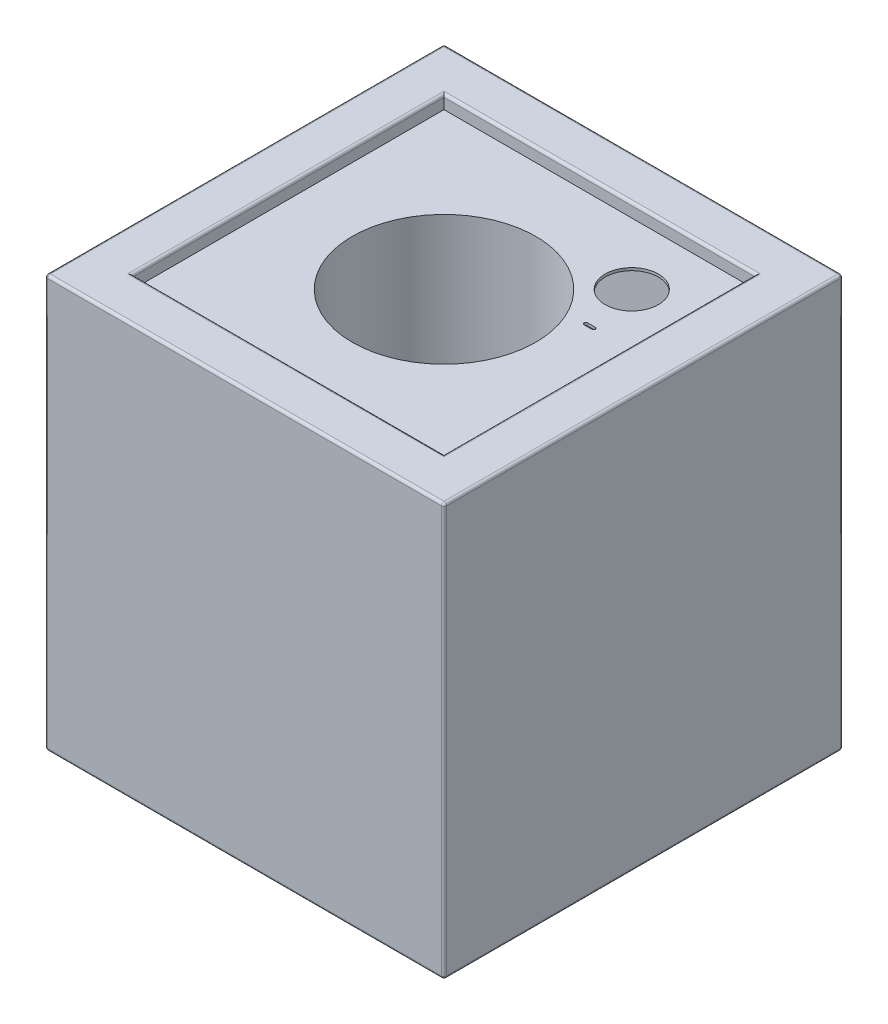
SolidWorks part; units mm, degrees
ref_plane "Front Plane" through (0, 0, 0) normal (0, 0, 1) x (1, 0, 0)
ref_plane "Top Plane" through (0, 0, 0) normal (0, 1, 0) x (1, 0, 0)
ref_plane "Right Plane" through (0, 0, 0) normal (1, 0, 0) x (0, 0, -1)
sketch "Sketch2" plane through (0, 0, 0) normal (0, 1, 0) x (1, 0, 0)
  line L1 (-150, 150) -> (150, 150)
  line L2 (-150, 150) -> (-150, -150)
  line L3 (-150, -150) -> (150, -150)
  line L4 (150, 150) -> (150, -150)
  line L5 (-150, 150) -> (150, -150) construction
  line L6 (-150, -150) -> (150, 150) construction
  point P0 (0, 0)
  dimension "D1" = 300
extrude "Boss-Extrude1" add sketch "Sketch2" along normal blind 10
sketch "Sketch3" plane through (0, 10, 0) normal (0, 1, 0) x (1, 0, 0)
  line L1 (-150, 150) -> (150, 150)
  line L2 (-150, 150) -> (-150, -150)
  line L3 (-150, -150) -> (150, -150)
  line L4 (150, 150) -> (150, -150)
  line L5 (-150, 150) -> (150, -150) construction
  line L6 (-150, -150) -> (150, 150) construction
  line L7 (-140, 140) -> (140, 140)
  line L8 (-140, 140) -> (-140, -140)
  line L9 (-140, -140) -> (140, -140)
  line L10 (140, 140) -> (140, -140)
  line L11 (-140, 140) -> (140, -140) construction
  line L12 (-140, -140) -> (140, 140) construction
  point P0 (0, 0)
  point P7 (0, 0)
  dimension "D1" = 10
extrude "Boss-Extrude2" add sketch "Sketch3" along normal blind 290
ref_plane "Plane1" through (0, 13, 0) normal (0, 1, 0) x (1, 0, 0)
sketch "Sketch4" plane through (0, 13, 0) normal (0, 1, 0) x (1, 0, 0)
  line L1 (-137, 137) -> (137, 137)
  line L2 (-137, 137) -> (-137, -137)
  line L3 (-137, -137) -> (137, -137)
  line L4 (137, 137) -> (137, -137)
  line L5 (-137, 137) -> (137, -137) construction
  line L6 (-137, -137) -> (137, 137) construction
  point P0 (0, 0)
  dimension "D1" = 274
extrude "Boss-Extrude3" add sketch "Sketch4" along normal blind 10 separate body
sketch "Sketch5" plane through (0, 23, 0) normal (0, 1, 0) x (1, 0, 0)
  line L1 (-137, 137) -> (137, 137)
  line L2 (-137, 137) -> (-137, -137)
  line L3 (-137, -137) -> (137, -137)
  line L4 (137, 137) -> (137, -137)
  line L5 (-137, 137) -> (137, -137) construction
  line L6 (-137, -137) -> (137, 137) construction
  line L7 (-127, 127) -> (127, 127)
  line L8 (-127, 127) -> (-127, -127)
  line L9 (-127, -127) -> (127, -127)
  line L10 (127, 127) -> (127, -127)
  line L11 (-127, 127) -> (127, -127) construction
  line L12 (-127, -127) -> (127, 127) construction
  point P0 (0, 0)
  point P7 (0, 0)
  dimension "D1" = 10
extrude "Boss-Extrude4" add sketch "Sketch5" along normal blind 277
ref_plane "Plane2" through (0, 33, 0) normal (0, 1, 0) x (1, 0, 0)
sketch "Sketch6" plane through (0, 33, 0) normal (0, 1, 0) x (1, 0, 0)
  line L1 (-117, 117) -> (117, 117)
  line L2 (-117, 117) -> (-117, -117)
  line L3 (-117, -117) -> (117, -117)
  line L4 (117, 117) -> (117, -117)
  line L5 (-117, 117) -> (117, -117) construction
  line L6 (-117, -117) -> (117, 117) construction
  point P0 (0, 0)
  dimension "D1" = 234
extrude "Boss-Extrude5" add sketch "Sketch6" along normal blind 20 separate body
sketch "Sketch7" plane through (0, 53, 0) normal (0, 1, 0) x (1, 0, 0)
  line L0 (117, -117) -> (117, 117) construction
  line L1 (-117, 117) -> (117, 117)
  line L2 (-117, 117) -> (-117, -117)
  line L3 (-117, -117) -> (117, -117)
  line L4 (117, 117) -> (117, -117)
  line L5 (-117, 117) -> (117, -117) construction
  line L6 (-117, -117) -> (117, 117) construction
  line L7 (-117, -117) -> (117, -117) construction
  line L9 (-97, 97) -> (97, 97)
  line L10 (-97, 97) -> (-97, -97)
  line L11 (-97, -97) -> (97, -97)
  line L12 (97, 97) -> (97, -97)
  line L13 (-97, 97) -> (97, -97) construction
  line L14 (-97, -97) -> (97, 97) construction
  point P0 (0, 0)
  point P10 (0, 0)
  dimension "D1" = 20
extrude "Boss-Extrude6" add sketch "Sketch7" along normal blind 247 contours L2 L1 L4 L3 | L10 L9 L12 L11
sketch "Sketch8" plane through (0, 53, 0) normal (0, 1, 0) x (1, 0, 0)
  circle A0 centre (0, 0) radius 71
extrude "Boss-Extrude7" add sketch "Sketch8" along normal blind 2
sketch "Sketch9" plane through (0, 55, 0) normal (0, 1, 0) x (1, 0, 0)
  circle A0 centre (0, 0) radius 71
  circle A1 centre (0, 0) radius 69
extrude "Boss-Extrude8" add sketch "Sketch9" along normal blind 245
ref_plane "Plane4" through (0, 244, 0) normal (0, 1, 0) x (1, 0, 0)
sketch "Sketch10" plane through (0, 244, 0) normal (0, 1, 0) x (1, 0, 0)
  line L1 (-97, 97) -> (97, 97)
  line L2 (-97, 97) -> (-97, -97)
  line L3 (-97, -97) -> (97, -97)
  line L4 (97, 97) -> (97, -97)
  circle A0 centre (0, 0) radius 71
extrude "Boss-Extrude9" add sketch "Sketch10" along normal blind 2
sketch "Sketch11" plane through (0, 246, 0) normal (0, 1, 0) x (1, 0, 0)
  line L1 (-97, -97) -> (97, -97)
  line L2 (-97, -97) -> (-97, 97)
  line L3 (-97, 97) -> (97, 97)
  line L4 (97, -97) -> (97, 97)
  line L5 (-97, -97) -> (97, 97) construction
  line L6 (-97, 97) -> (97, -97) construction
  line L7 (-95, 95) -> (95, 95)
  line L8 (-95, 95) -> (-95, -95)
  line L9 (-95, -95) -> (95, -95)
  line L10 (95, 95) -> (95, -95)
  line L11 (-95, 95) -> (95, -95) construction
  line L12 (-95, -95) -> (95, 95) construction
  circle A0 centre (0, 0) radius 73
  circle A1 centre (-0.8541, 0.8541) radius 72.2079
  circle A2 centre (0, 0) radius 71
  dimension "D1" = 2
extrude "Boss-Extrude11" add sketch "Sketch11" along normal blind 52 contours L10 L9 L8 L7 | L4 L3 L2 L1
sketch "Sketch12" plane through (0, 246, 0) normal (0, 1, 0) x (1, 0, 0)
  line L0 (-97, -97) -> (97, 97) construction
  circle A0 centre (70.5929, 70.5929) radius 20
extrude "Cut-Extrude1" cut sketch "Sketch12" against normal blind 52 and the other way blind 200 contours A0
sketch "Sketch16" plane through (0, 246, 0) normal (0, 1, 0) x (1, 0, 0)
  circle A0 centre (0, 0) radius 73
  circle A1 centre (0, 0) radius 71
extrude "Boss-Extrude14" add sketch "Sketch16" along normal blind 52
sketch "Sketch17" plane through (0, 298, 0) normal (0, 1, 0) x (1, 0, 0)
  line L1 (-97, 97) -> (97, 97)
  line L2 (-97, 97) -> (-97, -97)
  line L3 (-97, -97) -> (97, -97)
  line L4 (97, 97) -> (97, -97)
  line L5 (-97, 97) -> (97, -97) construction
  line L6 (-97, -97) -> (97, 97) construction
  circle A0 centre (0, 0) radius 69
extrude "Boss-Extrude15" add sketch "Sketch17" along normal blind 2
sketch "Sketch18" plane through (0, 300, 0) normal (0, 1, 0) x (1, 0, 0)
  line L1 (-150, 150) -> (150, 150)
  line L2 (-150, 150) -> (-150, -150)
  line L3 (-150, -150) -> (150, -150)
  line L4 (150, 150) -> (150, -150)
  line L5 (-150, 150) -> (150, -150) construction
  line L6 (-150, -150) -> (150, 150) construction
  line L7 (-117, 117) -> (117, 117)
  line L8 (-117, 117) -> (-117, -117)
  line L9 (-117, -117) -> (117, -117)
  line L10 (117, 117) -> (117, -117)
  line L11 (-117, 117) -> (117, -117) construction
  line L12 (-117, -117) -> (117, 117) construction
  point P0 (0, 0)
  point P7 (0, 0)
extrude "Boss-Extrude16" add sketch "Sketch18" along normal blind 10
fillet "Fillet1" radius 2 16 edges at (117, 310, 0) (0, 310, 117) (-117, 310, 0) (0, 310, -117) (150, 310, 0) (0, 310, -150) (-150, 310, 0) (0, 310, 150) (-150, 155, 150) (-150, 155, -150) (0, 0, -150) (-150, 0, 0) (150, 155, -150) (150, 0, 0) (150, 155, 150) (0, 0, 150)
sketch3d "3DSketch2"
  line L0 (70.5929, 246, -70.5929) -> (70.5929, 629.8029, -70.5929) construction
  line L1 (70.5929, 246, -70.5929) -> (70.5929, 244, -70.5929) construction
  circle A0 centre (70.5929, 300, -70.5929) radius 20
  point P2 (70.5929, 320, -70.5929)
extrude "Cut-Extrude6" cut sketch "3DSketch2" along direction (0, -1, 0) on the side of the normal blind 10
sketch "Sketch21" plane through (0, 246, 0) normal (0, 1, 0) x (1, 0, 0)
  circle A0 centre (80.6124, 39.4667) radius 1.5
extrude "Cut-Extrude7" cut sketch "Sketch21" against normal blind 10
sketch "Sketch22" plane through (0, 300, 0) normal (0, 1, 0) x (1, 0, 0)
  line L0 (74.5108, 32.162) -> (82.9108, 32.162)
  line L1 (82.9108, 32.162) -> (82.9108, 29.562)
  line L2 (82.9108, 29.562) -> (74.5108, 29.562)
  line L3 (74.5108, 29.562) -> (74.5108, 32.162)
  dimension "D1" = 8.4
  dimension "D2" = 2.6
extrude "Cut-Extrude8" cut sketch "Sketch22" against normal blind 10
fillet "Fillet2" radius 1.3 4 edges at (82.9108, 299, -29.562) (74.5108, 299, -29.562) (74.5108, 299, -32.162) (82.9108, 299, -32.162)
